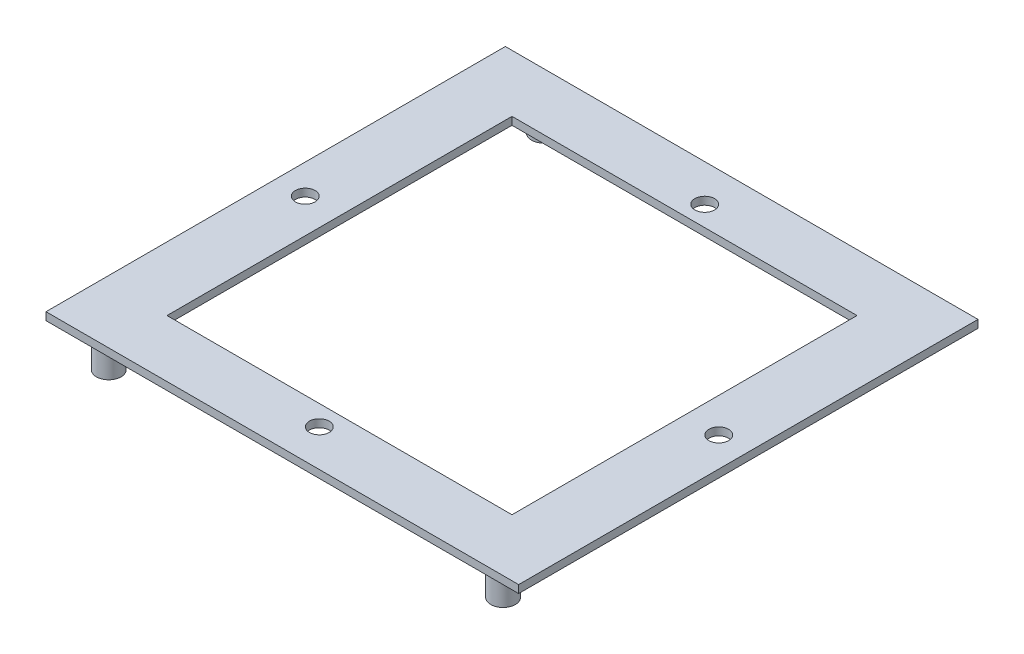
SolidWorks part; units mm, degrees
ref_plane "Front Plane" through (0, 0, 0) normal (0, 0, 1) x (1, 0, 0)
ref_plane "Top Plane" through (0, 0, 0) normal (0, 1, 0) x (1, 0, 0)
ref_plane "Right Plane" through (0, 0, 0) normal (1, 0, 0) x (0, 0, -1)
sketch "Sketch1" plane through (0, 0, 0) normal (0, 1, 0) x (1, 0, 0)
  line L1 (-47.95, -45.1) -> (47.95, -45.1)
  line L2 (-47.95, -45.1) -> (-47.95, 45.1)
  line L3 (-47.95, 45.1) -> (47.95, 45.1)
  line L4 (47.95, -45.1) -> (47.95, 45.1)
  line L5 (-47.95, -45.1) -> (47.95, 45.1) construction
  line L6 (-47.95, 45.1) -> (47.95, -45.1) construction
  point P0 (0, 0)
  point P6 (42.85, -37.5)
  point P7 (42.85, 36.2)
  point P8 (-42.85, 40)
  point P9 (-42.85, -40)
extrude "Boss-Extrude1" add sketch "Sketch1" along normal blind 1.58 contours L2 L1 L4 L3
sketch "Sketch2" plane through (0, 0, 0) normal (0, -1, 0) x (1, 0, 0)
  line L0 (-991.5515, 45.1) -> (49008.4485, 45.1) construction
  line L2 (-993.8223, -45.1) -> (49006.1777, -45.1) construction
  line L4 (-1000, 0) -> (49000, 0) construction
  line L5 (-47.95, -988.9501) -> (-47.95, 49011.0499) construction
  line L7 (47.95, -1000) -> (47.95, 49000) construction
  line L8 (47.95, 45.1) -> (47.95, -45.1) construction
  line L9 (0, -1000) -> (0, 49000) construction
  line L10 (-47.95, 0) -> (-41.95, 0) construction
  line L11 (-35, -35) -> (35, -35)
  line L12 (-35, -35) -> (-35, 35)
  line L13 (-35, 35) -> (35, 35)
  line L14 (35, -35) -> (35, 35)
  line L15 (-35, -35) -> (35, 35) construction
  line L16 (-35, 35) -> (35, -35) construction
  line L17 (-47.95, -45.1) -> (-47.95, 45.1) construction
  line L18 (47.95, 0) -> (41.95, 0) construction
  line L19 (0, -45.1) -> (0, -39.1) construction
  line L20 (47.95, -45.1) -> (-47.95, -45.1) construction
  line L21 (0, 45.1) -> (0, 39.1) construction
  line L22 (-47.95, 45.1) -> (47.95, 45.1) construction
  circle A0 centre (0, 39.1) radius 2
  circle A1 centre (41.95, 0) radius 2
  circle A2 centre (0, -39.1) radius 2
  circle A3 centre (-41.95, 0) radius 2
  point P14 (47.95, 0)
  point P15 (35, 35)
  point P17 (0, 0)
extrude "Cut-Extrude1" cut sketch "Sketch2" against normal through all both and the other way through all
sketch "Sketch3" plane through (0, 0, 0) normal (0, -1, 0) x (1, 0, 0)
  line L0 (41.055, 42.8625) -> (-38.955, 42.8625) construction
  line L1 (41.055, 42.8625) -> (41.055, -42.8675) construction
  line L2 (41.055, -42.8675) -> (37.245, -42.8675) construction
  line L3 (-38.955, 42.8625) -> (-38.955, -42.8675) construction
  line L4 (-38.955, -42.8675) -> (-36.415, -42.8675) construction
  line L5 (-36.415, -42.8675) -> (37.245, -42.8675) construction
  circle A0 centre (-38.955, 42.8625) radius 2.5
  circle A1 centre (41.055, 42.8625) radius 2.5
  circle A2 centre (37.245, -42.8675) radius 2.5
  circle A3 centre (-36.415, -42.8675) radius 2.5
  point P0 (41.055, 42.8625)
  dimension "D1" = 80.01
extrude "Boss-Extrude2" add sketch "Sketch3" along normal blind 6 contours A0 | A1 | A2 | A3
sketch "Sketch4" plane through (0, 0, 0) normal (0, -1, 0) x (1, 0, 0)
  line L0 (-47.95, 45.1) -> (-47.95, 46.6)
  line L1 (47.95, -45.1) -> (47.95, -46.6)
  line L3 (47.95, -46.6) -> (-47.95, -46.6)
  line L4 (47.95, -46.6) -> (47.95, -45.1)
  line L5 (47.95, -45.1) -> (-47.95, -45.1)
  line L6 (-47.95, -46.6) -> (-47.95, -45.1)
  line L7 (47.95, 45.1) -> (-47.95, 45.1)
  line L8 (47.95, 45.1) -> (47.95, 46.6)
  line L9 (47.95, 46.6) -> (-47.95, 46.6)
  line L10 (-47.95, 45.1) -> (-47.95, 46.6)
  line M2 (-35.2899, -45.1) -> (36.1199, -45.1)
  line M4 (38.3701, -45.1) -> (47.95, -45.1)
  line M6 (47.95, 45.1) -> (42.1702, 45.1)
  line M8 (39.9398, 45.1) -> (-37.8398, 45.1)
  line M10 (-40.0702, 45.1) -> (-47.95, 45.1)
  line M12 (-47.95, -45.1) -> (-37.5401, -45.1)
extrude "Boss-Extrude3" add sketch "Sketch4" against normal up to surface (1.58 mm away) contours L8 L9 L0 L7 M10 M8 M6 | L6 L3 L1 L5 M4 M2 M12 region at (0, 0, 45.85) region at (0, 0, -45.85) up to face at (0, 1.58, 37.1)
hole_wizard "M3x0.5 Tapped Hole1" positions "3DSketch1" profile "Sketch5" tap size "M3x0.5" standard "ANSI Metric"
sketch3d "3DSketch1"
  line L0 (-38.955, -6, 42.8625) -> (-38.955, 0, 42.8625) construction
  line L1 (41.055, -6, 42.8625) -> (41.055, 0, 42.8625) construction
  line L2 (37.245, -6, -42.8675) -> (37.245, 0, -42.8675) construction
  line L3 (-36.415, -6, -42.8675) -> (-36.415, 0, -42.8675) construction
  point P0 (-38.955, -6, 42.8625)
  point P4 (41.055, -6, 42.8625)
  point P8 (37.245, -6, -42.8675)
  point P12 (-36.415, -6, -42.8675)
sketch "Sketch5" plane through (-38.955, -6, 42.8625) normal (1, 0, 0) x (0, 0, -1)
  line L0 (0, 0) -> (0, 6.7511)
  line L1 (0, 6.7511) -> (1.25, 6)
  line L2 (1.25, 6) -> (1.25, 0)
  line L5 (1.25, 0) -> (0, 0)
  line L10 (0, 6.7511) -> (-1.25, 6) construction
  line L11 (0, -6.35) -> (0, 107.95) construction
  dimension "Tap Drill Dia." = 2.5
  dimension "Tap Drill Depth" = 6
  dimension "Drill Angle" = 118
cosmetic thread "Hole Thread1" parameters "D1"=6, "D2"=3
cosmetic thread "Hole Thread2" parameters "D1"=6, "D2"=3
cosmetic thread "Hole Thread3" parameters "D1"=6, "D2"=3
cosmetic thread "Hole Thread4" parameters "D1"=6, "D2"=3
